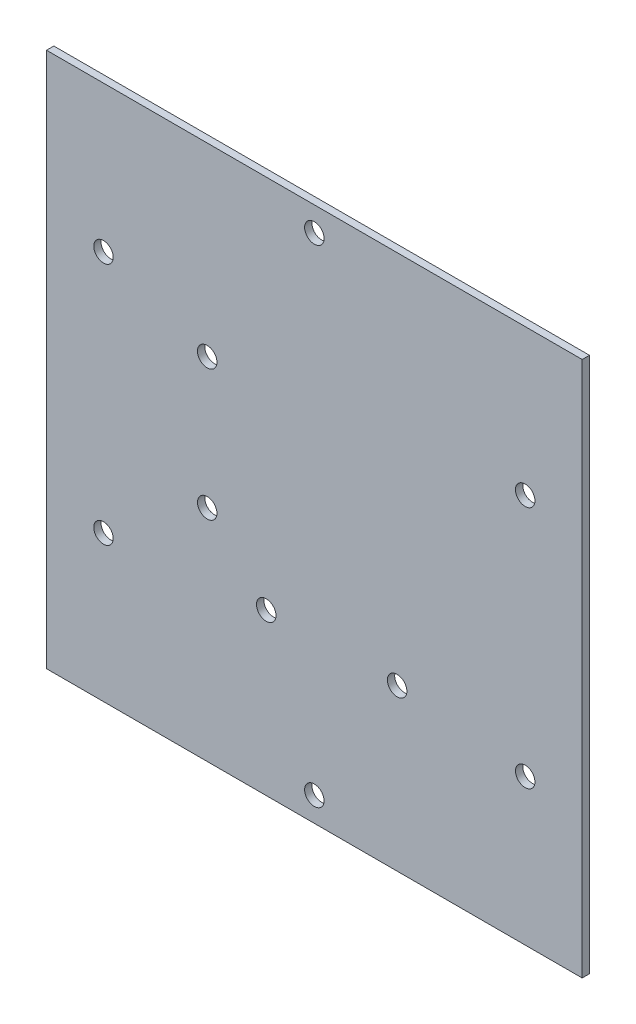
SolidWorks part; units mm, degrees
ref_plane "Piano frontale" through (0, 0, 0) normal (0, 0, 1) x (1, 0, 0)
ref_plane "Piano superiore" through (0, 0, 0) normal (0, 1, 0) x (1, 0, 0)
ref_plane "Piano destro" through (0, 0, 0) normal (1, 0, 0) x (0, 0, -1)
sketch "Schizzo1" plane through (0, 0, 0) normal (0, 0, 1) x (1, 0, 0)
  line L0 (-1000, 0) -> (49000, 0) construction
  line L1 (-100, 100) -> (100, 100) construction
  line L2 (-100, 100) -> (-100, -100) construction
  line L3 (-100, -100) -> (100, -100) construction
  line L4 (100, 100) -> (100, -100) construction
  line L5 (-100, 100) -> (100, -100) construction
  line L6 (-100, -100) -> (100, 100) construction
  line L7 (0, -1000) -> (0, 49000) construction
  line L8 (-110, 110) -> (110, 110)
  line L9 (110, 110) -> (110, -110)
  line L10 (-110, -110) -> (110, -110)
  line L11 (-110, 110) -> (-110, -110)
  circle A2 centre (0, 0) radius 100 construction
  circle A3 centre (0, 100) radius 4
  circle A4 centre (86.6025, 50) radius 4
  circle A5 centre (86.6025, -50) radius 4
  circle A6 centre (0, -100) radius 4
  circle A7 centre (-86.6025, -50) radius 4
  circle A8 centre (-86.6025, 50) radius 4
  point P0 (0, 0)
  point P15 (0, 100)
  point P27 (0, 0)
  dimension "D1" = 200
  dimension "D2" = 8
  dimension "D3" = 6
  dimension "D4" = 10
base flange "Base-Flangia1" sketch "Schizzo1" thickness 3 reverse thickness direction no parameters "D1"=1
sketch "Schizzo2" plane through (0, 0, 0) normal (0, 0, 1) x (1, 0, 0)
  line L7 (-110, 110) -> (-110, -110) construction
  line L9 (110, 110) -> (-110, 110) construction
  line L10 (-110, -110) -> (110, -110) construction
  line L11 (110, -110) -> (110, 110) construction
  circle A0 centre (-19.75, -44) radius 4
  circle A5 centre (-44, -19.75) radius 4
  circle A9 centre (-44, 34) radius 4
  circle A10 centre (34, -44) radius 4
  dimension "D1" = 8
  dimension "D4" = 8
  dimension "D3" = 8
  dimension "D10" = 8
  dimension "D2" = 90.25
  dimension "D5" = 66
  dimension "D6" = 66
  dimension "D7" = 76
  dimension "D8" = 76
  dimension "D9" = 66
  dimension "D11" = 66
  dimension "D12" = 90.25
extrude "Taglio-Estrusione1" cut sketch "Schizzo2" against normal through all normal cut yes
sketch "Linee di piegatura1" [suppressed] plane through (0, 0, 0) normal (0, 1, 0) x (1, 0, 0)
sketch "Casella di contorno1" [suppressed] plane through (0, 0, 0) normal (0, 1, 0) x (1, 0, 0)
sheet metal parameters "Lamiera1" thickness 3 parameters "D1"=1
flat pattern "Ripetizione piatta1" [suppressed]
sketch "Linee di piegatura2" plane through (0, 0, 0) normal (0, 1, 0) x (1, 0, 0)
sketch3d "Casella di contorno2" [suppressed]
  line L0 (-110, -110, 0) -> (110, -110, 0) construction
  line L1 (-110, 110, 0) -> (110, 110, 0) construction
  line L2 (-110, -110, 0) -> (-110, 110, 0) construction
  line L3 (110, -110, 0) -> (110, 110, 0) construction
sheet metal parameters "Lamiera2" thickness 3 parameters "D1"=1
flat pattern "Ripetizione piatta1"
sketch "Linee di piegatura2" plane through (0, 0, 0) normal (0, 1, 0) x (1, 0, 0)
sketch3d "Casella di contorno2" [suppressed]
  line L0 (-110, -110, 0) -> (110, -110, 0) construction
  line L1 (-110, 110, 0) -> (110, 110, 0) construction
  line L2 (-110, -110, 0) -> (-110, 110, 0) construction
  line L3 (110, -110, 0) -> (110, 110, 0) construction
